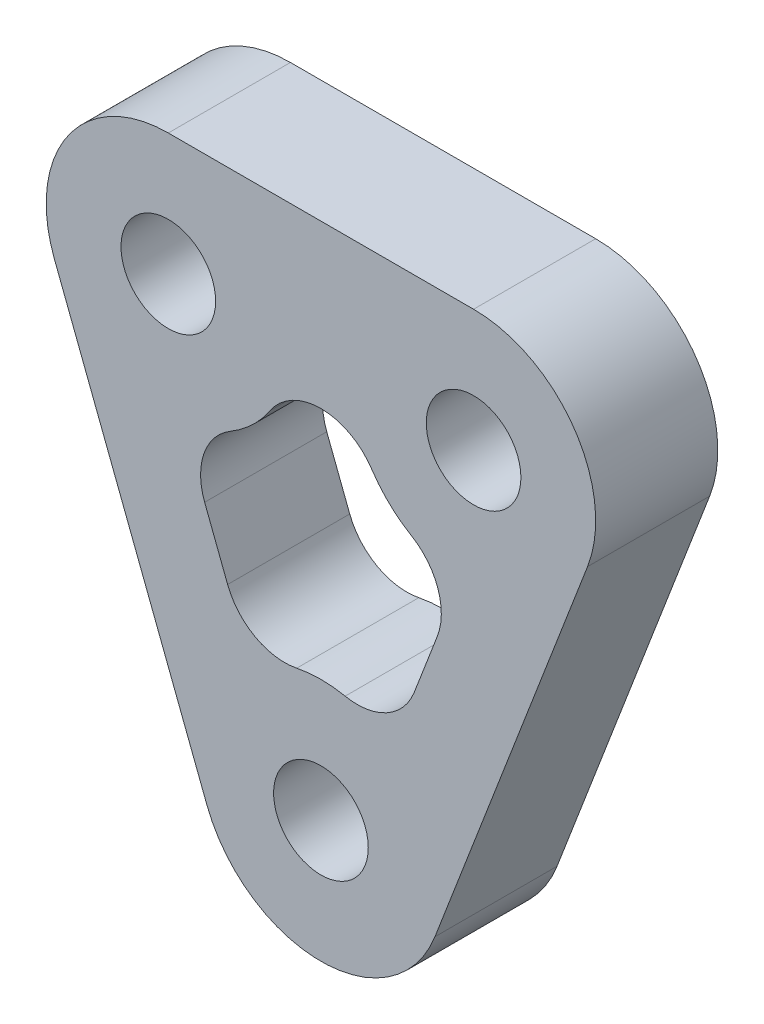
SolidWorks part; units mm, degrees
material "Thornel Mat VMA"
ref_plane "前视基准面" through (0, 0, 0) normal (0, 0, 1) x (1, 0, 0)
ref_plane "上视基准面" through (0, 0, 0) normal (0, 1, 0) x (1, 0, 0)
ref_plane "右视基准面" through (0, 0, 0) normal (1, 0, 0) x (0, 0, -1)
sketch "草图1" plane through (0, 0, 0) normal (0, 0, 1) x (1, 0, 0)
  line L0 (0, 0) -> (0, 16124.8174) construction
  line L1 (-8.7334, 11.5641) -> (-3.7334, -1.4359)
  line L2 (-5, 17) -> (5, 17)
  line L3 (8.7334, 11.5641) -> (3.7334, -1.4359)
  line L4 (-4.543, 9.0262) -> (-2.3237, 3.2559)
  line L5 (-1, 13) -> (1, 13)
  line L6 (4.543, 9.0262) -> (2.3237, 3.2559)
  circle A0 centre (0, 0) radius 1.55
  circle A1 centre (-5, 13) radius 1.55
  circle A2 centre (-5, 13) radius 4
  circle A3 centre (0, 0) radius 4
  circle A4 centre (5, 13) radius 4
  circle A5 centre (5, 13) radius 1.55
  point P17 (0, 17)
  dimension "D3" = 3.1
  dimension "D4" = 8
  dimension "D5" = 8
  dimension "D1" = 10
  dimension "D2" = 13
  dimension "D6" = 3
extrude "凸台-拉伸1" add sketch "草图1" along normal blind 4 contours A3 L4 A2 L1 | L3 A4 L6 A3 | A4 A5 | A2 A1 | L5 L0 L2 A2 | L0 L5 A4 L2 | A3 L0 A0 | L0 A3 A0 region at (1.1855, 3.7017, 0) region at (-1.1437, 15.5111, 0) region at (1.1437, 15.5111, 0) region at (4.9972, 5.5395, 0) region at (-4.9972, 5.5395, 0) region at (-2.0988, 10.4133, 0) region at (2.2516, 15.7484, 0)
fillet "圆角1" radius 2 6 edges at (-4.543, 9.0262, 2) (-2.3237, 3.2559, 2) (2.3237, 3.2559, 2) (4.543, 9.0262, 2) (1, 13, 2) (-1, 13, 2)
fillet "圆角2" radius 2 1 edges at (0, 12.8891, 2)
